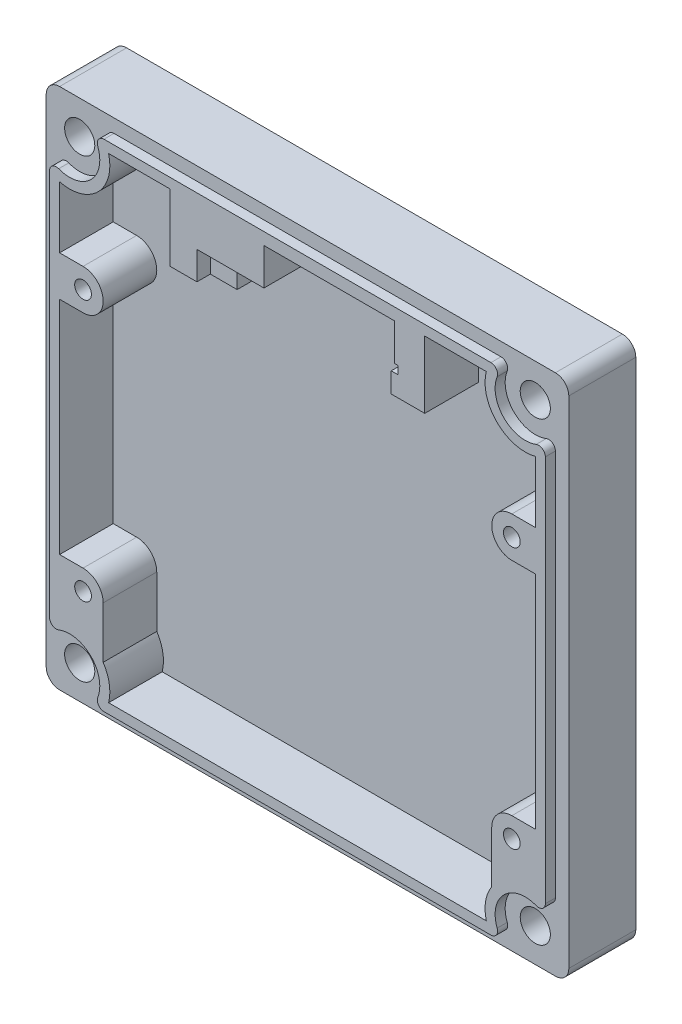
SolidWorks part; units mm, degrees
ref_plane "Front Plane" through (0, 0, 0) normal (0, 0, 1) x (1, 0, 0)
ref_plane "Top Plane" through (0, 0, 0) normal (0, 1, 0) x (1, 0, 0)
ref_plane "Right Plane" through (0, 0, 0) normal (1, 0, 0) x (0, 0, -1)
sketch "Sketch1" plane through (0, 0, 0) normal (0, 0, 1) x (1, 0, 0)
  line L1 (-39, -39) -> (39, -39)
  line L2 (-39, -39) -> (-39, 39)
  line L3 (-39, 39) -> (39, 39)
  line L4 (39, -39) -> (39, 39)
  line L5 (-39, -39) -> (39, 39) construction
  line L6 (-39, 39) -> (39, -39) construction
  point P0 (0, 0)
  dimension "D1" = 78
  dimension "D2" = 78
extrude "Boss-Extrude1" add sketch "Sketch1" along normal blind 10
fillet "Fillet1" radius 2 4 edges at (-39, -39, 5) (39, -39, 5) (39, 39, 5) (-39, 39, 5)
sketch "Sketch5" plane through (0, 0, 0) normal (0, 0, -1) x (-1, 0, 0)
  line L0 (-39, -37) -> (-39, 37) construction
  line L1 (-39, 39) -> (-29, 39)
  line L2 (-39, 39) -> (-39, 29)
  line L3 (-39, 29) -> (-34, 29)
  line L4 (-29, 39) -> (-29, 34)
  line L5 (-37, 39) -> (37, 39) construction
  arc A0 (-34, 29) -> (-29, 34) centre (-34, 34) ccw
  dimension "D1" = 5
extrude "Cut-Extrude2" [suppressed] cut sketch "Sketch5" against normal blind 10
ref_axis "Axis1" through (0, 0, -1.5) along (0, 0, 1)
sketch "Sketch9" [suppressed] plane through (0, 0, 0) normal (0, 0, -1) x (-1, 0, 0)
  line L2 (-29.1, 39) -> (-34, 39)
  line L3 (-39, 34) -> (-39, 29.1)
  line L4 (-29, 39) -> (-34, 39) construction
  line L5 (-39, 34) -> (-39, 29) construction
  line L6 (-39, 29) -> (-34, 29) construction
  line L7 (-29, 34) -> (-29, 39) construction
  arc A0 (-34, 39) -> (-39, 34) centre (-34, 34) ccw construction
  arc A1 (-34, 39) -> (-39, 34) centre (-34, 34) ccw
  dimension "D1" = 0.1
  dimension "D2" = 0.1
extrude "Extrude-Thin2" [suppressed] add sketch "Sketch9" against normal up to next thin thin type one direction reverse wall 0.5
pattern_circular "CirPattern1" [suppressed] count 4 over 360 about axis through (0, 0, -1.5) along (0, 0, 1) of bodies 112
shell "Shell1" thickness 3.5 removed face at (0, 0, 10)
sketch "Sketch3" plane through (0, 0, 0) normal (0, 0, 1) x (1, 0, 0)
  line L0 (37, 39) -> (-37, 39) construction
  line L1 (39, -37) -> (39, 37) construction
  circle A0 centre (34, 34) radius 5
  dimension "D1" = 10
extrude "Boss-Extrude2" add sketch "Sketch3" along normal up to surface (10 mm away) from offset 1 separate body up to face at (0, 0, 10)
pattern_circular "CirPattern5" count 4 over 360 about axis through (0, 0, -1.5) along (0, 0, 1) of bodies 102
combine bodies "Combine1" operation type add bodies to combine 101 106 102 107 108
sketch "Sketch4" plane through (0, 0, 10) normal (0, 0, 1) x (1, 0, 0)
  circle A0 centre (34, 34) radius 2.25
  dimension "D1" = 4.5
extrude "Cut-Extrude1" cut sketch "Sketch4" against normal through all
sketch "Sketch10" [suppressed] plane through (0, 0, 10) normal (0, 0, -1) x (-1, 0, 0)
  circle A0 centre (-34, 34) radius 2.25 construction
  circle A1 centre (-34, 34) radius 2.25
extrude "Extrude-Thin3" [suppressed] add sketch "Sketch10" along normal up to surface (10 mm away) thin up to face at (36.25, 34, 0) thin type one direction wall 0.5
pattern_circular "CirPattern6" count 4 over 360 about axis through (0, 0, -1.5) along (0, 0, 1) of "Cut-Extrude1", "Extrude-Thin3"
other "Move Face1" face at (31.4148, -31.4148, 6.75) face at (-31.4148, -31.4148, 6.75) face at (-31.4148, 31.4148, 6.75) face at (31.4148, 31.4148, 6.75) offset 1 parameters "D1"=1
sketch "Sketch7" plane through (0, 0, 10) normal (0, 0, 1) x (1, 0, 0)
  line L4 (35.5, -28.1905) -> (35.5, 28.1905)
  line L5 (-28.1905, -35.5) -> (28.1905, -35.5)
  line L6 (-35.5, 28.1905) -> (-35.5, -28.1905)
  line L7 (28.1905, 35.5) -> (-28.1905, 35.5)
  line L8 (35.5, -28.1905) -> (35.5, 28.1905)
  line L9 (-28.1905, -35.5) -> (28.1905, -35.5)
  line L10 (-35.5, 28.1905) -> (-35.5, -28.1905)
  line L11 (28.1905, 35.5) -> (-28.1905, 35.5)
  arc A4 (35.5, -28.1905) -> (28.1905, -35.5) centre (34, -34) ccw
  arc A5 (35.5, -28.1905) -> (28.1905, -35.5) centre (34, -34) ccw
  arc A6 (-28.1905, -35.5) -> (-35.5, -28.1905) centre (-34, -34) ccw
  arc A7 (-28.1905, -35.5) -> (-35.5, -28.1905) centre (-34, -34) ccw
  arc A8 (-35.5, 28.1905) -> (-28.1905, 35.5) centre (-34, 34) ccw
  arc A9 (-35.5, 28.1905) -> (-28.1905, 35.5) centre (-34, 34) ccw
  arc A10 (28.1905, 35.5) -> (35.5, 28.1905) centre (34, 34) ccw
  arc A11 (28.1905, 35.5) -> (35.5, 28.1905) centre (34, 34) ccw
  dimension "D1" = 0
extrude "Extrude-Thin1" add sketch "Sketch7" along normal blind 1.5 thin thin type one direction wall 1.5
fillet "Fillet2" radius 1 8 edges at (37, -30.6459, 10.75) (30.6459, -37, 10.75) (-30.6459, -37, 10.75) (-37, -30.6459, 10.75) (-30.6459, 37, 10.75) (-37, 30.6459, 10.75) (30.6459, 37, 10.75) (37, 30.6459, 10.75)
chamfer "Chamfer1" [suppressed] distance 3 angle 45
sketch "Sketch11" plane through (0, 0, 3.5) normal (0, 0, 1) x (1, 0, 0)
  line L0 (-35.5, -28.1905) -> (-35.5, -20)
  line L1 (-35.5, 28.1905) -> (-35.5, -28.1905) construction
  line L2 (-35.5, -20) -> (-32, -20)
  line L3 (-29, -23) -> (-29, -30.6834)
  line L5 (-35.5, 28.1905) -> (-35.5, -28.1905) construction
  line L7 (-35.5, 19) -> (-32, 19)
  line L8 (-35.5, 19) -> (-35.5, 13)
  line L9 (-35.5, 13) -> (-32, 13)
  arc A2 (-32, -20) -> (-29, -23) centre (-32, -23) cw
  arc A3 (-28.1905, -35.5) -> (-35.5, -28.1905) centre (-34, -34) ccw construction
  arc A4 (-35.5, -28.1905) -> (-29, -30.6834) centre (-34, -34) cw
  arc A5 (-32, 19) -> (-32, 13) centre (-32, 16) cw
  dimension "D1" = 3
  dimension "D2" = 32
  dimension "D3" = 23
  dimension "D4" = 6
  dimension "D5" = 39
extrude "Boss-Extrude3" add sketch "Sketch11" along normal up to surface (8 mm away) up to face at (0, 0, 11.5)
sketch "Sketch12" plane through (0, 0, 11.5) normal (0, 0, 1) x (1, 0, 0)
  circle A0 centre (-32, -23) radius 1.25
  circle A1 centre (-32, 16) radius 1.25
  dimension "D1" = 2.5
extrude "Cut-Extrude3" cut sketch "Sketch12" against normal blind 5
mirror "Mirror1" about plane through (0, 0, 0) normal (1, 0, 0) of "Cut-Extrude3", "Boss-Extrude3"
sketch "Sketch13" plane through (0, 0, 3.5) normal (0, 0, 1) x (1, 0, 0)
  line L0 (28.1905, 35.5) -> (-28.1905, 35.5) construction
  line L1 (-19, 35.5) -> (19, 35.5)
  line L2 (-19, 35.5) -> (-19, 25.5)
  line L3 (-19, 25.5) -> (19, 25.5)
  line L4 (19, 35.5) -> (19, 25.5)
  line L5 (0, 35.5) -> (0, 0) construction
  dimension "D1" = 38
  dimension "D2" = 10
extrude "Boss-Extrude4" add sketch "Sketch13" along normal up to surface (8 mm away) up to face at (30.75, -23, 11.5)
sketch "Sketch14" plane through (0, 0, 11.5) normal (0, 0, 1) x (1, 0, 0)
  line L0 (-11, 25.5) -> (-11, 28.5)
  line L1 (-19, 25.5) -> (19, 25.5) construction
  line L2 (-11, 28.5) -> (-15, 28.5)
  line L3 (-15, 28.5) -> (-15, 29.7)
  line L4 (-15, 29.7) -> (15, 29.7)
  line L5 (15, 29.7) -> (15, 28.5)
  line L6 (15, 28.5) -> (14, 28.5)
  line L7 (14, 28.5) -> (14, 25.5)
  line L8 (14, 25.5) -> (-11, 25.5)
  line L9 (0, 29.7) -> (0, 0) construction
  dimension "D1" = 1.2
  dimension "D2" = 30
  dimension "4" = 4
  dimension "D4" = 1
  dimension "D5" = 3
extrude "Cut-Extrude4" cut sketch "Sketch14" against normal up to surface (8 mm away) up to face at (0, 4.4713, 3.5)
sketch "Sketch15" plane through (0, 0, 11.5) normal (0, 0, 1) x (1, 0, 0)
  line L1 (-5, 29.7) -> (14.5, 29.7)
  line L2 (-5, 29.7) -> (-5, 35.2)
  line L3 (-5, 35.2) -> (14.5, 35.2)
  line L4 (14.5, 29.7) -> (14.5, 35.2)
  line L5 (15, 29.7) -> (-15, 29.7) construction
  line L6 (-15, 29.7) -> (-15, 28.5) construction
  dimension "D1" = 10
  dimension "D2" = 19.5
  dimension "D3" = 5.5
extrude "Cut-Extrude5" cut sketch "Sketch15" against normal up to surface (8 mm away)
sketch "Sketch16" plane through (0, 0, 11.5) normal (0, 0, 1) x (1, 0, 0)
  line L1 (-15, 28.5) -> (-11, 28.5)
  line L2 (-15, 28.5) -> (-15, 25.5)
  line L3 (-15, 25.5) -> (-11, 25.5)
  line L4 (-11, 28.5) -> (-11, 25.5)
extrude "Cut-Extrude6" cut sketch "Sketch16" against normal blind 2
